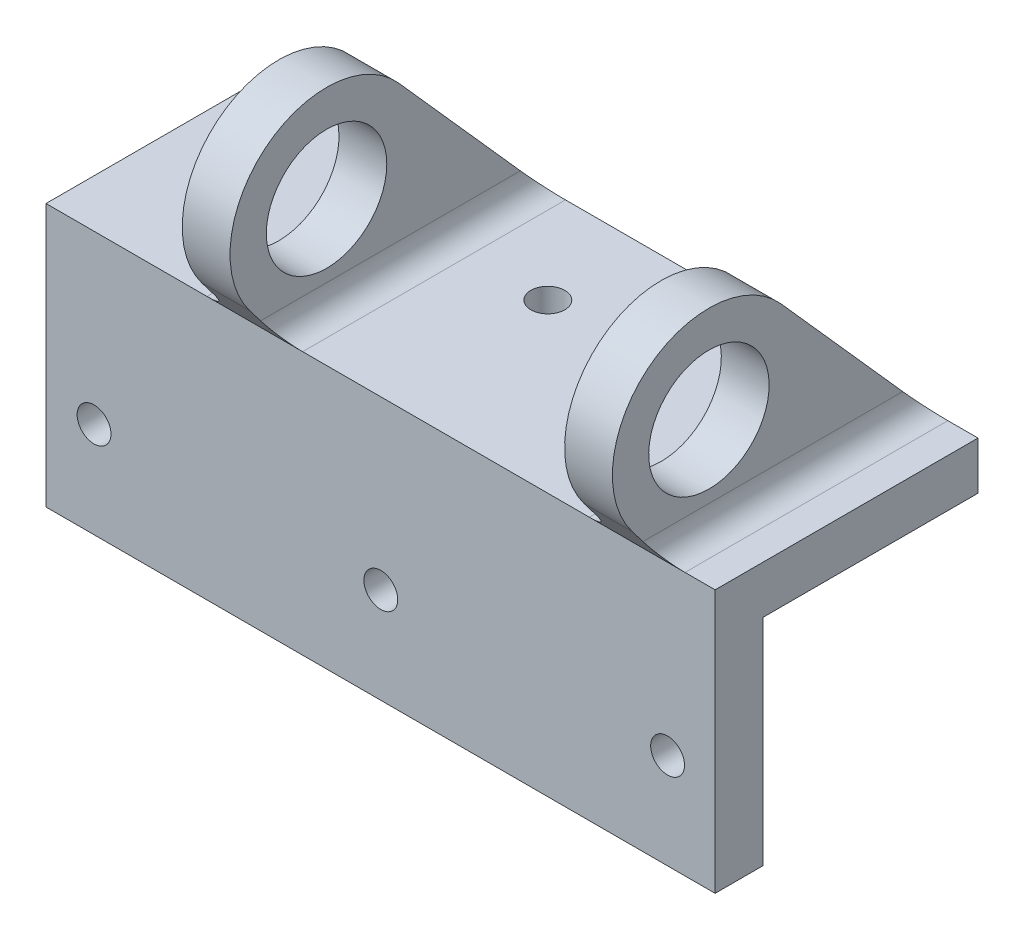
SolidWorks part; units mm, degrees
ref_plane "Front Plane" through (0, 0, 0) normal (0, 0, 1) x (1, 0, 0)
ref_plane "Top Plane" through (0, 0, 0) normal (0, 1, 0) x (1, 0, 0)
ref_plane "Right Plane" through (0, 0, 0) normal (1, 0, 0) x (0, 0, -1)
sketch "Sketch1" plane through (0, 0, 0) normal (0, 0, 1) x (1, 0, 0)
  line L1 (44.45, -14.2875) -> (-44.45, -14.2875)
  line L2 (44.45, -14.2875) -> (44.45, 14.2875)
  line L3 (44.45, 14.2875) -> (-44.45, 14.2875)
  line L4 (-44.45, -14.2875) -> (-44.45, 14.2875)
  line L5 (44.45, -14.2875) -> (-44.45, 14.2875) construction
  line L6 (44.45, 14.2875) -> (-44.45, -14.2875) construction
  circle A3 centre (-38.0669, -1.5875) radius 2.25
  circle A4 centre (0.0331, -1.5875) radius 2.25
  circle A5 centre (38.1331, -1.5875) radius 2.25
  point P0 (0, 0)
  dimension "D2" = 15.875
  dimension "D5" = 4.5
  dimension "D1" = 12.7
  dimension "D3" = 38.1
  dimension "D4" = 88.9
  dimension "D7" = 38.1
  dimension "D6" = 3
extrude "Boss-Extrude1" add sketch "Sketch1" along normal blind 6.35
sketch "Sketch2" plane through (0, 14.2875, 0) normal (0, 1, 0) x (1, 0, 0)
  line L0 (-12.7, 28.575) -> (-12.7, -6.35) construction
  line L1 (-44.45, -6.35) -> (44.45, -6.35)
  line L2 (-44.45, -6.35) -> (-44.45, 28.575)
  line L3 (-44.45, 28.575) -> (44.45, 28.575)
  line L4 (44.45, -6.35) -> (44.45, 28.575)
  line L5 (44.45, 0) -> (-44.45, 0) construction
  line L6 (30.1, 28.575) -> (30.1, -6.35) construction
  line L7 (44.45, -6.35) -> (-44.45, -6.35) construction
  line L8 (-12.7, 11.1125) -> (-4, 11.1125) construction
  line L9 (-4, -6.35) -> (21.4, -6.35)
  line L10 (-4, -6.35) -> (-4, 28.575) construction
  line L11 (-4, 28.575) -> (21.4, 28.575)
  line L12 (21.4, -6.35) -> (21.4, 28.575) construction
  line L13 (21.4, 11.1125) -> (30.1, 11.1125) construction
  line L15 (30.925, 28.575) -> (37.275, 28.575)
  line L16 (30.925, 28.575) -> (30.925, -6.35)
  line L17 (30.925, -6.35) -> (37.275, -6.35)
  line L18 (37.275, 28.575) -> (37.275, -6.35)
  line L19 (-13.525, 28.575) -> (-19.875, 28.575)
  line L20 (-13.525, 28.575) -> (-13.525, -6.35)
  line L21 (-13.525, -6.35) -> (-19.875, -6.35)
  line L22 (-19.875, 28.575) -> (-19.875, -6.35)
  circle A0 centre (0, 15.875) radius 2.25
  circle A1 centre (-38.1, 15.875) radius 2.25
  circle A2 centre (38.1, 15.875) radius 2.25 construction
  line M3 (44.45, 0) -> (-44.45, 0)
  line M4 (-44.45, 0) -> (-44.45, -6.35)
  line M5 (-44.45, -6.35) -> (44.45, -6.35)
  line M6 (44.45, -6.35) -> (44.45, 0)
  dimension "D3" = 4.5
  dimension "D1" = 15.875
  dimension "D2" = 12.7
  dimension "D4" = 38.1
  dimension "D5" = 38.1
  dimension "D6" = 0
  dimension "D7" = 12.7
  dimension "D8" = 8
  dimension "D9" = 25.4
  dimension "D10" = 6.35
  dimension "D11" = 9.525
  dimension "D12" = 9.525
  dimension "D13" = 6.35
extrude "Boss-Extrude2" add sketch "Sketch2" along normal blind 6.35 contours L22 L3 L2 A1 M3 | L3 L22 L20 M3 | L22 M3 M4 M5 | L22 L1 L20 M3 | L3 L20 L16 A0 M3 | L20 L1 L16 M3 M5 | L18 L3 L16 M3 | L3 L18 L4 M3 | L18 M3 M5 M6 | L18 L16 L1 M3 region at (-32.1625, 14.2875, 3.175) region at (-16.7, 14.2875, 3.175) region at (-32.0249, 14.2875, -14.2507) region at (8.7, 14.2875, 3.175) region at (-16.7, 14.2875, -14.2875) region at (8.8103, 14.2875, -14.2674) region at (34.1, 14.2875, 3.175) region at (34.1, 14.2875, -14.2875) region at (40.8625, 14.2875, 3.175) region at (40.8625, 14.2875, -14.2875)
extrude "Boss-Extrude3" add sketch "Sketch2<4>" along normal blind 38.1 contours L3 L22 L20 M3 | L18 L3 L16 M3 region at (-16.7, 14.2875, -14.2875) region at (34.1, 14.2875, -14.2875)
sketch "Sketch2<4>" plane through (0, 14.2875, 0) normal (0, 1, 0) x (1, 0, 0) same geometry as "Sketch2"
sketch "Sketch3" plane through (-19.875, 0, 0) normal (-1, 0, 0) x (0, 0, 1)
  line L0 (0, 52.3875) -> (0, 20.6375) construction
  line L1 (6.35, 20.6375) -> (-28.575, 20.6375) construction
  line L2 (6.35, 20.6375) -> (10.1996, 25.6876)
  line L3 (-9.582, 41.9869) -> (-28.575, 20.6375)
  line L4 (6.35, 20.6375) -> (0, 20.6375)
  circle A0 centre (0, 33.4625) radius 8
  circle A1 centre (0, 33.4625) radius 12.825
  line M4 (0, 20.6375) -> (0, 52.3875)
  line M5 (0, 52.3875) -> (-28.575, 52.3875)
  line M6 (-28.575, 52.3875) -> (-28.575, 20.6375)
  dimension "D2" = 16
  dimension "D1" = 12.825
extrude "Boss-Extrude4" add sketch "Sketch3" against normal up to surface (6.35 mm away) contours A1 A0 M4 | A1 L4 L2 region at (-19.875, 21.6854, 5.8312) region at (-19.875, 22.2262, 5.5634) up to face at (-13.525, 36.5125, -14.2875)
extrude "Cut-Extrude1" cut sketch "Sketch3<4>" against normal blind 97.028 contours A1 L3 M4 M5 M6 | A0 M4 region at (-19.875, 42.0989, -18.3514) region at (-19.875, 33.4625, -3.3953)
sketch "Sketch3<4>" plane through (-19.875, 0, 0) normal (-1, 0, 0) x (0, 0, 1) same geometry as "Sketch3"
sketch "Sketch4" plane through (37.275, 0, 0) normal (1, 0, 0) x (0, 0, -1)
  line L3 (28.575, 20.6375) -> (9.582, 41.9869)
  line L4 (-10.1996, 25.6876) -> (-6.35, 20.6375)
  line L5 (-6.35, 20.6375) -> (28.575, 20.6375)
  line L6 (28.575, 20.6375) -> (9.582, 41.9869)
  line L7 (-10.1996, 25.6876) -> (-6.35, 20.6375)
  line L8 (-6.35, 20.6375) -> (28.575, 20.6375)
  circle A0 centre (0, 33.4625) radius 8 construction
  arc A1 (9.582, 41.9869) -> (-10.1996, 25.6876) centre (0, 33.4625) ccw
  arc A2 (9.582, 41.9869) -> (-10.1996, 25.6876) centre (0, 33.4625) ccw
  arc A3 (0, 25.4625) -> (0, 41.4625) centre (0, 33.4625) ccw construction
  circle A4 centre (0, 33.4625) radius 8
  arc A5 (0, 25.4625) -> (0, 41.4625) centre (0, 33.4625) ccw
  arc M5 (0, 41.4625) -> (0, 25.4625) centre (0, 33.4625) cw
  line M6 (0, 25.4625) -> (0, 20.6375)
  line M7 (0, 20.6375) -> (28.575, 20.6375)
  line M8 (28.575, 20.6375) -> (9.582, 41.9869)
  arc M9 (9.582, 41.9869) -> (0, 46.2875) centre (0, 33.4625) ccw
  line M10 (0, 46.2875) -> (0, 41.4625)
  dimension "D1" = 0
extrude "Boss-Extrude5" add sketch "Sketch4" against normal up to surface (6.35 mm away) contours M10 M5 M6 M7 M8 M9 | A4 A2 L7 L8 M10 M6 region at (37.275, 29.5738, -11.8401) region at (37.275, 20.9243, 3.175) up to face at (30.925, 32.9167, -7.7696)
fillet "Fillet1" radius 3.175 4 edges at (37.275, 20.6375, -11.1125) (30.925, 20.6375, -11.1125) (-19.875, 20.6375, -11.1125) (-13.525, 20.6375, -11.1125)
